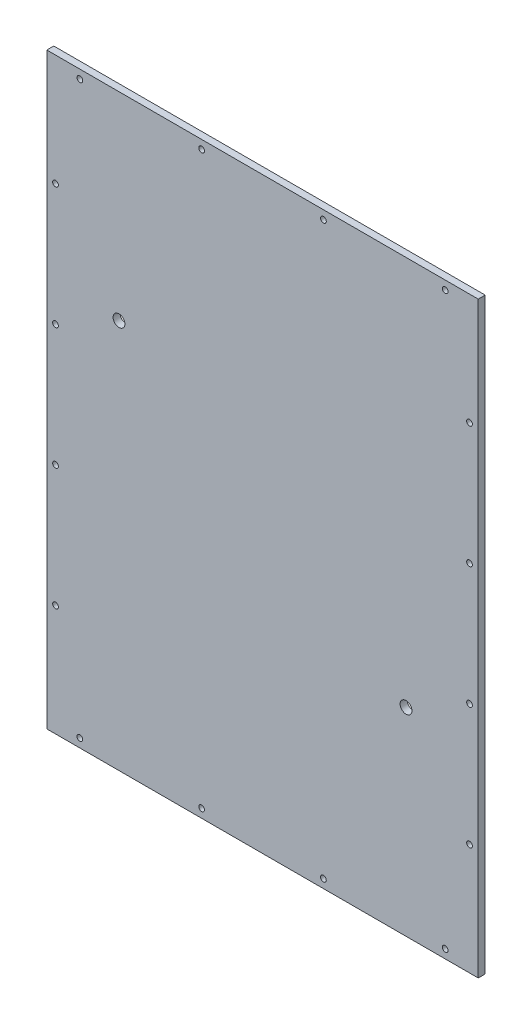
SolidWorks part; units mm, degrees
material "PVC hart"
ref_plane "Front Plane" through (0, 0, 0) normal (0, 0, 1) x (1, 0, 0)
ref_plane "Top Plane" through (0, 0, 0) normal (0, 1, 0) x (1, 0, 0)
ref_plane "Right Plane" through (0, 0, 0) normal (1, 0, 0) x (0, 0, -1)
sketch "Sketch1" plane through (0, 0, 0) normal (0, 0, 1) x (1, 0, 0)
  line L0 (0, 42.2863) -> (0, -35.7084) construction
  line L1 (-31.3624, 0) -> (45.6927, 0) construction
  line L2 (-130, 175) -> (130, 175)
  line L3 (130, 175) -> (130, -175)
  line L4 (130, -175) -> (-130, -175)
  line L5 (-130, -175) -> (-130, 175)
  dimension "D1" = 260
  dimension "D2" = 350
extrude "Boss-Extrude1" add sketch "Sketch1" along normal blind 58
fillet "Fillet1" radius 54 4 edges at (-130, 0, 58) (0, -175, 58) (130, 0, 58) (0, 175, 58)
sketch "Skizze1" plane through (0, 0, 0) normal (0, 0, -1) x (-1, 0, 0)
  line L0 (0, 110.5595) -> (0, -132.4992) construction
  line L1 (-73.1906, 0) -> (91.9751, 0) construction
  line L3 (-130, 175) -> (130, 175)
  line L4 (-130, 175) -> (-130, -175)
  line L5 (-130, -175) -> (130, -175)
  line L6 (130, 175) -> (130, -175)
  line L7 (-124, 169) -> (124, 169)
  line L8 (-124, 169) -> (-124, -169)
  line L9 (-124, -169) -> (124, -169)
  line L10 (124, 169) -> (124, -169)
  dimension "D1" = 6
  dimension "D2" = 6
extrude "Schnitt-Linear austragen1" cut sketch "Skizze1" against normal blind 4
hole_wizard "M4 Tapped Hole1" positions "Skizze3" profile "Skizze2" tap size "M4" standard "DIN"
sketch "Skizze3" plane through (0, 0, 0) normal (0, 0, -1) x (-1, 0, 0)
  line L0 (0, 193.3503) -> (0, -97.2891) construction
  line L2 (-155.1219, 0) -> (178.3178, 0) construction
  point P0 (-105, 164)
  point P2 (-35, 164)
  point P4 (-119, 105)
  point P6 (-119, 35)
  dimension "D1" = 35
  dimension "D2" = 105
  dimension "D3" = 35
  dimension "D4" = 105
  dimension "D5" = 164
  dimension "D6" = 164
  dimension "D7" = 119
  dimension "D8" = 119
sketch "Skizze2" plane through (105, 164, 0) normal (1, 0, 0) x (0, 1, 0)
  line L0 (0, 0) -> (0, 12.4914)
  line L1 (0, 12.4914) -> (1.65, 11.5)
  line L2 (1.65, 11.5) -> (1.65, 0)
  line L5 (1.65, 0) -> (0, 0)
  line L10 (0, 12.4914) -> (-1.65, 11.5) construction
  line L11 (0, -6.35) -> (0, 107.95) construction
  dimension "Bohrerdurchmesser" = 3.3
  dimension "Bohrungstiefe" = 11.5
  dimension "Spitzenwinkel" = 118
cosmetic thread "Bohrungsgewinde1" parameters "D1"=8, "D2"=4
cosmetic thread "Bohrungsgewinde2" parameters "D1"=8, "D2"=4
cosmetic thread "Bohrungsgewinde3" parameters "D1"=8, "D2"=4
cosmetic thread "Bohrungsgewinde4" parameters "D1"=8, "D2"=4
mirror "Spiegeln1" about plane through (0, 0, 0) normal (0, 1, 0) of "M4 Tapped Hole1"
mirror "Spiegeln2" about plane through (0, 0, 0) normal (1, 0, 0) of "M4 Tapped Hole1", "Spiegeln1"
sketch "Sketch2" plane through (0, 0, 4) normal (0, 0, -1) x (-1, 0, 0)
  line L1 (-130, 175) -> (130, 175)
  line L2 (-130, 175) -> (-130, -175)
  line L3 (-130, -175) -> (130, -175)
  line L4 (130, 175) -> (130, -175)
extrude "Cut-Extrude1" cut sketch "Sketch2" against normal through all
hole_wizard "M8 Tapped Hole1" positions "Sketch4" profile "Sketch3" tap size "M8" standard "DIN" end condition through all
sketch "Sketch4" plane through (0, 0, 0) normal (0, 0, -1) x (-1, 0, 0)
  line L0 (2.2, 0) -> (-2.2, 0) construction
  line L1 (0, 2.2) -> (0, -2.2) construction
  point P0 (-82.5, -55)
  dimension "D1" = 55
  dimension "D2" = 82.5
cosmetic thread "Hole Thread1" parameters "D2"=8
sketch "Sketch3" plane through (82.5, -55, 0) normal (1, 0, 0) x (0, 1, 0)
  line L0 (0, 0) -> (0, 4)
  line L1 (0, 4) -> (3.4, 4)
  line L2 (3.4, 4) -> (3.4, 0)
  line L5 (3.4, 0) -> (0, 0)
  line L11 (0, -6.35) -> (0, 107.95) construction
  dimension "Thru Tap Drill Dia." = 6.8
  dimension "Thru Tap Drill Depth" = 4
ref_axis "Axis1" through (0, 0, -0.2) along (0, 0, 1)
pattern_circular "CirPattern1" count 2 over 360 about axis through (0, 0, -0.2) along (0, 0, 1) of "M8 Tapped Hole1"
